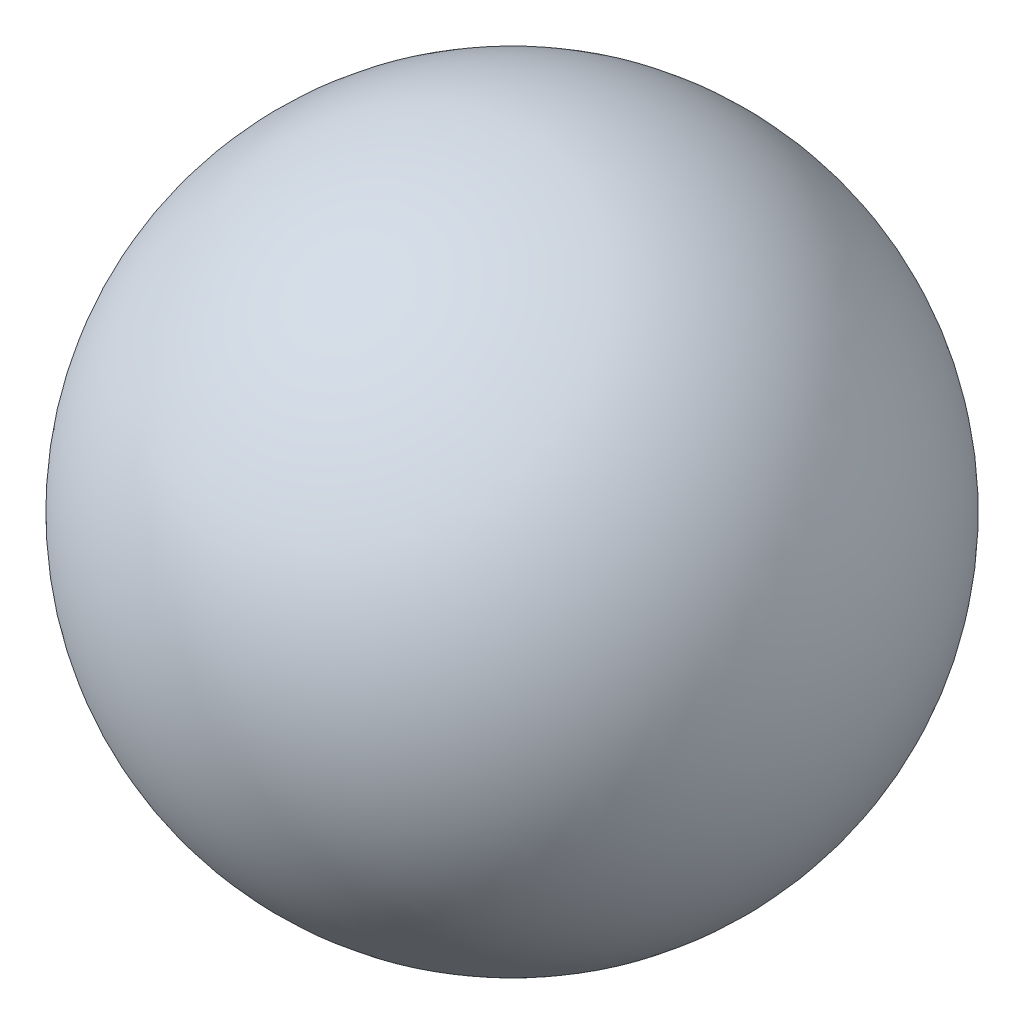
SolidWorks part; units mm, degrees
ref_plane "Front Plane" through (0, 0, 0) normal (0, 0, 1) x (1, 0, 0)
ref_plane "Top Plane" through (0, 0, 0) normal (0, 1, 0) x (1, 0, 0)
ref_plane "Right Plane" through (0, 0, 0) normal (1, 0, 0) x (0, 0, -1)
sketch "Sketch1" plane through (0, 0, 0) normal (0, 0, 1) x (1, 0, 0)
  line L0 (0, 810) -> (0, -810)
  arc A0 (0, -810) -> (0, 810) centre (0, 0) ccw
  dimension "D1" = 1620
revolve "Revolve1" add sketch "Sketch1" angle 360 about L0
